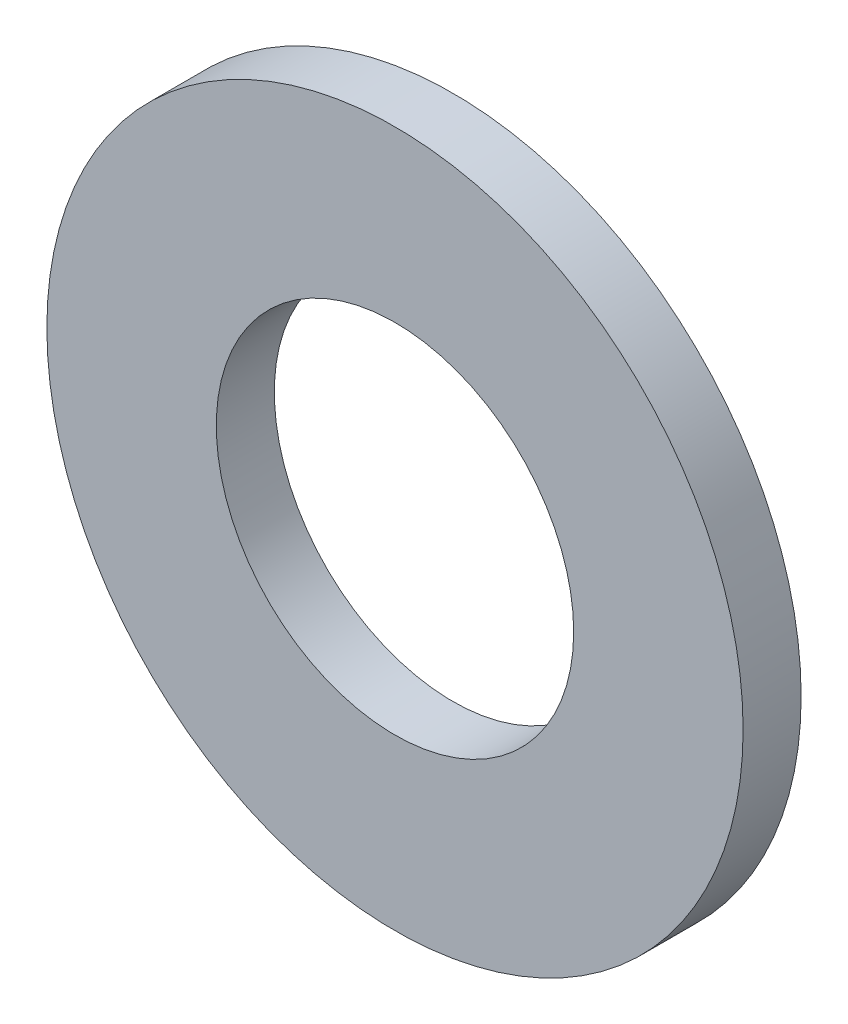
SolidWorks part; units mm, degrees
material "Aluminum Bronze"
ref_plane "Front Plane" through (0, 0, 0) normal (0, 0, 1) x (1, 0, 0)
ref_plane "Top Plane" through (0, 0, 0) normal (0, 1, 0) x (1, 0, 0)
ref_plane "Right Plane" through (0, 0, 0) normal (1, 0, 0) x (0, 0, -1)
ref_axis "Centerline" through (0, 0, -88.99) along (0, 0, 1)
sketch "Sketch1" plane through (0, 0, 0) normal (0, 0, 1) x (1, 0, 0)
  circle A0 centre (0, 0) radius 9.525
  circle A1 centre (0, 0) radius 4.8895
  dimension "D1" = 19.05
  dimension "D2" = 9.779
extrude "Boss-Extrude1" add sketch "Sketch1" along normal blind 1.5875
